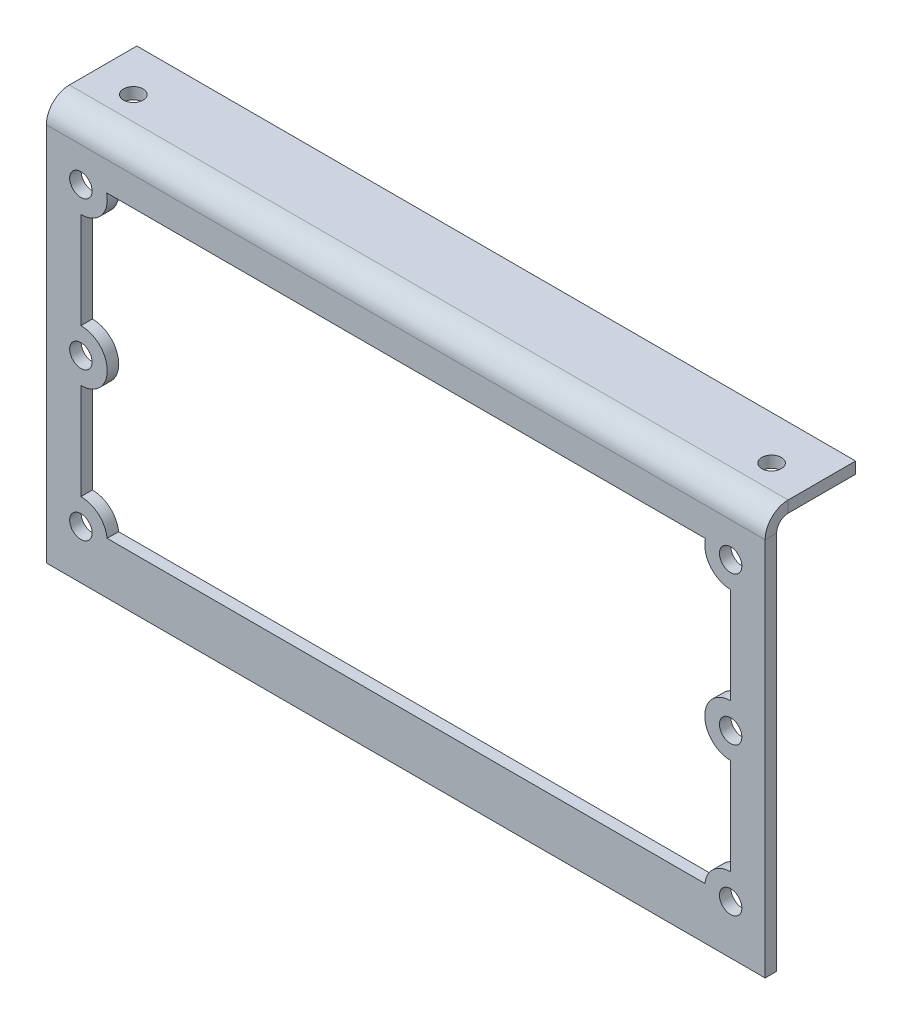
SolidWorks part; units mm, degrees
note: The reader was unsure of these and kept them because the rebuilt part matched: flange length of "Edge-Flange2".
ref_plane "Front Plane" through (0, 0, 0) normal (0, 0, 1) x (1, 0, 0)
ref_plane "Top Plane" through (0, 0, 0) normal (0, 1, 0) x (1, 0, 0)
ref_plane "Right Plane" through (0, 0, 0) normal (1, 0, 0) x (0, 0, -1)
sketch "Sketch3" plane through (0, 0, 0) normal (0, 0, 1) x (1, 0, 0)
  line L1 (-63.2811, 48.5524) -> (61.7189, 48.5524)
  line L2 (-63.2811, 48.5524) -> (-63.2811, -21.4476)
  line L3 (-63.2811, -21.4476) -> (61.7189, -21.4476)
  line L4 (61.7189, 48.5524) -> (61.7189, -21.4476)
  dimension "D1" = 125
  dimension "D2" = 70
base flange "Base-Flange1" sketch "Sketch3" thickness 2 reverse thickness direction no parameters "D1"=2
edge flange "Edge-Flange2" sketch "Sketch15" flange angle 90 flange length 15.7366 flange position material inside bend radius 2 thickness 2 relief rectangular parameters "D1"=0.7366, "D6"=10
sketch "Sketch15" plane through (0, 48.5524, -2) normal (0, 1, 0) x (1, 0, 0)
  line L0 (61.7189, 0) -> (-63.2811, 0) construction
  line L1 (61.7189, 0) -> (-63.2811, 0)
  line L2 (-63.2811, 0) -> (-63.2811, 13.7366)
  line L3 (-63.2811, 13.7366) -> (61.7189, 13.7366)
  line L4 (61.7189, 13.7366) -> (61.7189, 0)
bend "EdgeBend2" bend radius 2 bend angle 90 parameters "D5"=1
extrude "Cut-Extrude3" cut sketch "Sketch18" against normal blind 10
sketch "Sketch18" plane through (-99.7526, 247.5103, -2) normal (0, 0, -1) x (1, 0, 0)
  line L0 (36.4715, 202.958) -> (36.4715, 268.958) construction
  line L1 (155.4715, 207.958) -> (42.4715, 207.958)
  line L2 (155.4715, 207.958) -> (155.4715, 259.958)
  line L3 (155.4715, 259.958) -> (42.4715, 259.958)
  line L4 (42.4715, 207.958) -> (42.4715, 259.958)
  line L5 (161.4715, 268.958) -> (161.4715, 202.958) construction
  line L6 (36.4715, 268.958) -> (161.4715, 268.958) construction
  line L7 (161.4715, 202.958) -> (36.4715, 202.958) construction
  dimension "D1" = 6
  dimension "D2" = 6
  dimension "D3" = 9
  dimension "D4" = 5
sketch "Sketch23" plane through (0, 0, 0) normal (0, 0, 1) x (1, 0, 0)
  line L1 (61.7189, 44.5524) -> (-63.2811, 44.5524) construction
  circle A1 centre (-57.1915, 12.8024) radius 4.5
  circle A2 centre (-57.1915, -12.9476) radius 4.5
  circle A3 centre (55.7189, -12.9476) radius 4.5
  circle A4 centre (55.7189, 12.8024) radius 4.5
  circle A5 centre (-57.1915, 38.5524) radius 4.5
  circle A6 centre (55.7189, 38.5524) radius 4.5
  dimension "D1" = 9
  dimension "D2" = 9
  dimension "D3" = 9
  dimension "D4" = 9
  dimension "D5" = 9
  dimension "D6" = 9
  dimension "D7" = 25.75
  dimension "D8" = 25.75
  dimension "D9" = 6
extrude "Boss-Extrude1" add sketch "Sketch23" against normal blind 2
hole_wizard "PSU bracket MB holes" positions "Sketch21" profile "Sketch22" hole size "M3" standard "AS" end condition through all
sketch "Sketch21" plane through (-99.7526, 40.5524, 598.4925) normal (0, -1, 0) x (1, 0, 0)
  line L0 (36.4715, -614.2291) -> (36.4715, -602.4925) construction
  line L1 (161.4715, -602.4925) -> (161.4715, -614.2291) construction
  line L2 (161.4715, -614.2291) -> (36.4715, -614.2291) construction
  point P0 (43.4715, -606.6109)
  point P2 (154.4715, -606.6109)
  dimension "D1" = 7
  dimension "D2" = 7
  dimension "D3" = 7.6182
sketch "Sketch22" plane through (-56.2811, 40.5524, -8.1184) normal (1, 0, 0) x (0, 0, -1)
  line L0 (0, 0) -> (0, 8)
  line L1 (0, 8) -> (1.7, 8)
  line L2 (1.7, 8) -> (1.7, 0)
  line L5 (1.7, 0) -> (0, 0)
  line L11 (0, -6.35) -> (0, 107.95) construction
  dimension "Thru Hole Dia." = 3.4
  dimension "Thru Hole Depth" = 8
hole_wizard "M3.5 Clearance Hole1" positions "Sketch25" profile "Sketch26" hole size "M3.5" standard "ANSI Metric" end condition through all
sketch "Sketch25" plane through (-98.7526, 247.5103, -2) normal (0, 0, -1) x (1, 0, 0)
  line L0 (160.4715, 202.958) -> (35.4715, 202.958) construction
  point P0 (41.4715, 260.458)
  point P3 (41.4715, 234.708)
  point P6 (41.4715, 208.958)
  point P10 (154.4715, 208.958)
  point P14 (154.4715, 234.708)
  point P17 (154.4715, 260.458)
  dimension "D1" = 113
  dimension "D2" = 51.5
  dimension "D3" = 6
  dimension "D4" = 25.75
sketch "Sketch26" plane through (-57.2811, -12.9476, -2) normal (1, 0, 0) x (0, 1, 0)
  line L0 (0, 0) -> (0, 2)
  line L1 (0, 2) -> (1.95, 2)
  line L2 (1.95, 2) -> (1.95, 0)
  line L5 (1.95, 0) -> (0, 0)
  line L11 (0, -6.35) -> (0, 107.95) construction
  dimension "Thru Hole Dia." = 3.9
  dimension "Thru Hole Depth" = 2
sketch "Bend-Lines1" [suppressed] plane through (0, 0, 0) normal (0, 1, 0) x (1, 0, 0)
sketch "Bounding-Box1" [suppressed] plane through (0, 0, 0) normal (0, 1, 0) x (1, 0, 0)
sheet metal parameters "Sheet-Metal2" thickness 2 parameters "D1"=10
flat pattern "Flat-Pattern2" [suppressed]
sketch "Bend-Lines2" plane through (0, 0, 0) normal (0, 1, 0) x (1, 0, 0)
sketch3d "Bounding-Box2" [suppressed]
  line L0 (-64.4462, -35.515, 0) -> (71.679, -35.515, 0) construction
  line L1 (-64.4462, 42.3769, 0) -> (71.679, 42.3769, 0) construction
  line L2 (-64.4462, -35.515, 0) -> (-64.4462, 42.3769, 0) construction
  line L3 (71.679, -35.515, 0) -> (71.679, 42.3769, 0) construction
sheet metal parameters "Sheet-Metal4" thickness 2 parameters "D1"=10
flat pattern "Flat-Pattern2"
sketch "Bend-Lines2" plane through (0, 0, 0) normal (0, 0, 1) x (1, 0, 0)
  line L0 (61.7189, 41.1797) -> (-65.2811, 41.1797) construction
  line L1 (61.7189, 41.1797) -> (-65.2811, 41.1797) construction
sketch3d "Bounding-Box2" [suppressed]
  line L0 (-65.2811, -21.4476, 0) -> (61.7189, -21.4476, 0) construction
  line L1 (-65.2811, 55.5436, 0) -> (61.7189, 55.5436, 0) construction
  line L2 (-65.2811, -21.4476, 0) -> (-65.2811, 55.5436, 0) construction
  line L3 (61.7189, -21.4476, 0) -> (61.7189, 55.5436, 0) construction
bend of the flat pattern "Flatten-<EdgeBend2>1"
sheet metal parameters "Sheet-Metal8" thickness 2 parameters "D1"=10
flat pattern "Flat-Pattern2"
sketch "Bend-Lines2" plane through (0, 0, 0) normal (0, 0, 1) x (1, 0, 0)
  line L0 (61.7189, 41.1797) -> (-65.2811, 41.1797) construction
  line L1 (61.7189, 41.1797) -> (-65.2811, 41.1797) construction
sketch3d "Bounding-Box2" [suppressed]
  line L0 (-65.2811, -21.4476, 0) -> (61.7189, -21.4476, 0) construction
  line L1 (-65.2811, 55.5436, 0) -> (61.7189, 55.5436, 0) construction
  line L2 (-65.2811, -21.4476, 0) -> (-65.2811, 55.5436, 0) construction
  line L3 (61.7189, -21.4476, 0) -> (61.7189, 55.5436, 0) construction
bend of the flat pattern "Flatten-<EdgeBend2>1"
sheet metal parameters "Sheet-Metal10" thickness 2 parameters "D1"=10
flat pattern "Flat-Pattern2"
sketch "Bend-Lines2" plane through (0, 0, 0) normal (0, 0, 1) x (1, 0, 0)
  line L0 (61.7189, 40.9086) -> (-63.2811, 40.9086) construction
  line L1 (61.7189, 40.9086) -> (-63.2811, 40.9086) construction
sketch3d "Bounding-Box2" [suppressed]
  line L0 (-63.2811, -21.4476, 0) -> (61.7189, -21.4476, 0) construction
  line L1 (-63.2811, 55.0013, 0) -> (61.7189, 55.0013, 0) construction
  line L2 (-63.2811, -21.4476, 0) -> (-63.2811, 55.0013, 0) construction
  line L3 (61.7189, -21.4476, 0) -> (61.7189, 55.0013, 0) construction
bend of the flat pattern "Flatten-<EdgeBend2>1"
sheet metal parameters "Sheet-Metal12" thickness 2 parameters "D1"=10
flat pattern "Flat-Pattern2"
sketch "Bend-Lines2" plane through (0, 0, 0) normal (0, 0, 1) x (1, 0, 0)
  line L0 (61.7189, 44.9086) -> (-63.2811, 44.9086) construction
  line L1 (61.7189, 44.9086) -> (-63.2811, 44.9086) construction
sketch3d "Bounding-Box2" [suppressed]
  line L0 (-63.2811, -21.4476, 0) -> (61.7189, -21.4476, 0) construction
  line L1 (-63.2811, 59.0013, 0) -> (61.7189, 59.0013, 0) construction
  line L2 (-63.2811, -21.4476, 0) -> (-63.2811, 59.0013, 0) construction
  line L3 (61.7189, -21.4476, 0) -> (61.7189, 59.0013, 0) construction
bend of the flat pattern "Flatten-<EdgeBend2>1"
sheet metal parameters "Sheet-Metal14" thickness 2 parameters "D1"=10
flat pattern "Flat-Pattern2"
sketch "Bend-Lines2" plane through (0, 0, 0) normal (0, 0, 1) x (1, 0, 0)
  line L0 (61.7189, 46.9086) -> (-63.2811, 46.9086) construction
  line L1 (61.7189, 46.9086) -> (-63.2811, 46.9086) construction
sketch3d "Bounding-Box2" [suppressed]
  line L0 (-63.2811, -21.4476, 0) -> (61.7189, -21.4476, 0) construction
  line L1 (-63.2811, 61.0013, 0) -> (61.7189, 61.0013, 0) construction
  line L2 (-63.2811, -21.4476, 0) -> (-63.2811, 61.0013, 0) construction
  line L3 (61.7189, -21.4476, 0) -> (61.7189, 61.0013, 0) construction
bend of the flat pattern "Flatten-<EdgeBend2>1"
